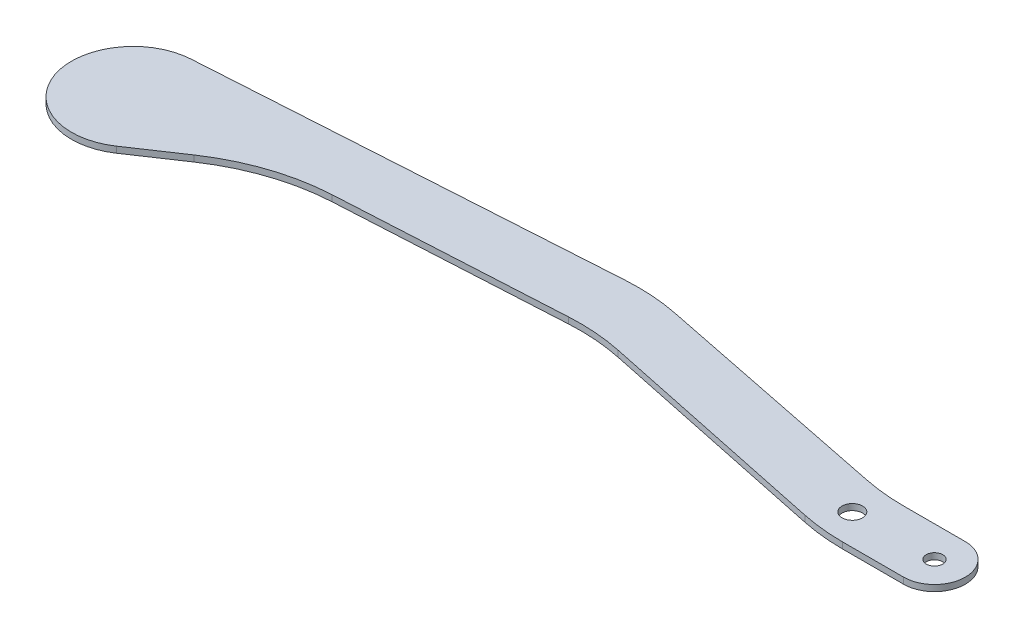
SolidWorks part; units mm, degrees
ref_plane "Front Plane" through (0, 0, 0) normal (0, 0, 1) x (1, 0, 0)
ref_plane "Top Plane" through (0, 0, 0) normal (0, 1, 0) x (1, 0, 0)
ref_plane "Right Plane" through (0, 0, 0) normal (1, 0, 0) x (0, 0, -1)
sketch "Sketch1" plane through (0, 0, 0) normal (0, 1, 0) x (1, 0, 0)
  line L0 (0, 0) -> (-350, 0) construction
  line L1 (0, 0) -> (40, 0) construction
  line L2 (0, 15) -> (40, 15)
  line L3 (0, -15) -> (40, -15)
  line L4 (-351.8754, 29.9413) -> (-333.2857, -24.9125) construction
  line L5 (-139.7849, 43.2259) -> (-4217.6379, -212.1962)
  line L6 (0, 15) -> (-4004.6012, 823.6244)
  line L7 (0, 15) -> (-5.9197, -13.7825) construction
  line L8 (-4217.6379, -212.1962) -> (-138.0533, 13.889)
  line L9 (-4004.6012, 823.6244) -> (-5.9197, -13.7825)
  line L10 (-333.2857, -24.9125) -> (-287.8235, 5.5889)
  line L11 (-5.9197, -13.7825) -> (0, -15)
  circle A0 centre (0, 0) radius 5
  circle A1 centre (-350, 0) radius 30
  circle A2 centre (40, 0) radius 4
  circle A3 centre (0, 0) radius 15
  circle A4 centre (40, 0) radius 15
  dimension "D1" = 10
  dimension "D4" = 8
  dimension "D5" = 60
  dimension "D6" = 30
  dimension "D7" = 165
  dimension "D2" = 350
  dimension "D3" = 40
  dimension "D8" = 165
  dimension "D9" = 135
  dimension "D10" = 150
extrude "Boss-Extrude1" add sketch "Sketch1" along normal blind 3 contours L8 A1 | A1 L8 | A1 L8 L9 L5 | A1 L10 L8 | A3 L6 L5 L9 | A3 A0 | A4 L2 A3 L3 | A4 A2 region at (-104.3815, 0, -20.1768) region at (20, 0, 0) region at (10.3066, 0, -10.3066) region at (50.3066, 0, -10.3066) region at (-256.3648, 0, -20.0554) region at (-350.7689, 0, -13.8751) region at (-310.7553, 0, 3.5404) region at (-349.359, 0, 11.5664)
fillet "Fillet1" radius 100 5 edges at (0, 1.5, -15) (-139.7849, 1.5, -43.2259) (-138.0533, 1.5, -13.889) (-287.8235, 1.5, -5.5889) (0, 1.5, 15)
